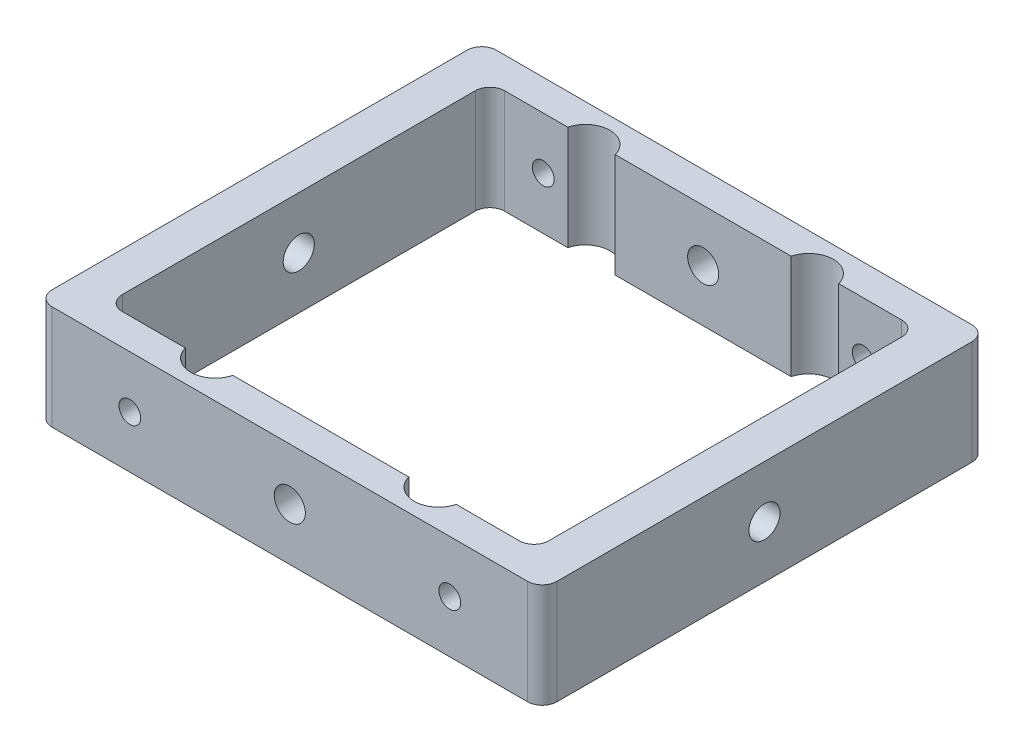
SolidWorks part; units mm, degrees
ref_plane "Front Plane" through (0, 0, 0) normal (0, 0, 1) x (1, 0, 0)
ref_plane "Top Plane" through (0, 0, 0) normal (0, 1, 0) x (1, 0, 0)
ref_plane "Right Plane" through (0, 0, 0) normal (1, 0, 0) x (0, 0, -1)
sketch "Sketch1" plane through (0, 0, 0) normal (0, 1, 0) x (1, 0, 0)
  line L1 (0, 0) -> (60, 0)
  line L2 (0, 0) -> (0, -6.32)
  line L3 (0, -6.32) -> (60, -6.32)
  line L4 (60, 0) -> (60, -6.32)
  dimension "D1" = 60
  dimension "D2" = 6.32
extrude "Boss-Extrude1" add sketch "Sketch1" along normal mid plane 21.28
sketch "Sketch2" plane through (0, 10.64, 0) normal (0, 1, 0) x (1, 0, 0)
  line L0 (0, 0) -> (0, -6.32) construction
  line L1 (0, -6.32) -> (60, -6.32) construction
  line L2 (60, -6.32) -> (60, 0) construction
  circle A0 centre (7.21, 1.25) radius 5
  circle A1 centre (52.79, 1.25) radius 5
  dimension "D1" = 7.21
  dimension "D3" = 7.21
  dimension "D2" = 7.57
  dimension "D4" = 7.57
extrude "Cut-Extrude1" cut sketch "Sketch2" against normal through all
sketch "Sketch3" plane through (60, 0, 0) normal (1, 0, 0) x (0, 0, -1)
  line L1 (-6.32, 10.64) -> (0, 10.64)
  line L2 (-6.32, 10.64) -> (-6.32, -10.64)
  line L3 (-6.32, -10.64) -> (0, -10.64)
  line L4 (0, 10.64) -> (0, -10.64)
extrude "Boss-Extrude2" add sketch "Sketch3" along normal blind 21.5
sketch "Sketch4" plane through (0, 0, 0) normal (-1, 0, 0) x (0, 0, 1)
  line L1 (0, 10.64) -> (6.32, 10.64)
  line L2 (0, 10.64) -> (0, -10.64)
  line L3 (0, -10.64) -> (6.32, -10.64)
  line L4 (6.32, 10.64) -> (6.32, -10.64)
extrude "Boss-Extrude3" add sketch "Sketch4" along normal blind 21.5
sketch "Sketch5" plane through (0, 0, 0) normal (0, 0, -1) x (-1, 0, 0)
  line L5 (-2.3688, -10.64) -> (21.5, -10.64) construction
  line L6 (21.5, 10.64) -> (13.5, 10.64)
  line L7 (21.5, 10.64) -> (21.5, -10.64)
  line L8 (21.5, -10.64) -> (13.5, -10.64)
  line L9 (13.5, 10.64) -> (13.5, -10.64)
  dimension "D1" = 8
extrude "Boss-Extrude6" add sketch "Sketch5" along normal blind 84.33
sketch "Sketch6" plane through (0, 0, 0) normal (0, 0, -1) x (-1, 0, 0)
  line L1 (-81.5, 10.64) -> (-73.5, 10.64)
  line L2 (-81.5, 10.64) -> (-81.5, -10.652)
  line L3 (-81.5, -10.652) -> (-73.5, -10.652)
  line L4 (-73.5, 10.64) -> (-73.5, -10.652)
  dimension "D1" = 8
extrude "Boss-Extrude7" add sketch "Sketch6" along normal blind 84.33
sketch "Sketch7" plane through (73.5, 0, 0) normal (-1, 0, 0) x (0, 0, 1)
  line L0 (-84.33, -10.652) -> (0, -10.652) construction
  line L1 (-84.33, 10.64) -> (-78.01, 10.64)
  line L2 (-84.33, 10.64) -> (-84.33, -10.652)
  line L3 (-84.33, -10.652) -> (-78.01, -10.652)
  line L4 (-78.01, 10.64) -> (-78.01, -10.652)
  dimension "D1" = 6.32
extrude "Boss-Extrude8" add sketch "Sketch7" along normal through all
sketch "Sketch9" plane through (0, 10.64, 0) normal (0, 1, 0) x (1, 0, 0)
  line L0 (-21.5, 84.33) -> (81.5, 84.33) construction
  circle A0 centre (7.21, 76.76) radius 5
  circle A1 centre (52.79, 76.76) radius 5
  dimension "D1" = 7.57
  dimension "D2" = 7.57
  dimension "D3" = 10
extrude "Cut-Extrude2" cut sketch "Sketch9" against normal through all
sketch "Sketch10" plane through (0, 0, -84.33) normal (0, 0, -1) x (-1, 0, 0)
  line L1 (-81.5, -10.64) -> (21.5, -10.64) construction
  line L2 (-30, -10.64) -> (-30, 10.64) construction
  line L3 (21.5, 10.64) -> (-81.5, 10.64) construction
  circle A0 centre (-62.6312, 0.005) radius 2.22
  circle A1 centre (2.6312, 0.005) radius 2.22
  dimension "D1" = 5
  dimension "D2" = 10.645
extrude "Cut-Extrude3" cut sketch "Sketch10" against normal through all
fillet "Fillet1" radius 3 8 edges at (-21.5, 0, 6.32) (81.5, 0, 6.32) (81.5, -0.006, -84.33) (-21.5, -0.006, -84.33) (-13.5, 0, -78.01) (-13.5, 0, 0) (73.5, -0.006, -78.01) (73.5, 0, 0)
sketch "Sketch13" plane through (0, 0, -84.33) normal (0, 0, -1) x (-1, 0, 0)
  line L1 (-78.5, 10.64) -> (-78.5, -10.652) construction
  line L2 (-78.5, -10.64) -> (18.5, -10.64) construction
  circle A0 centre (-30, 0.005) radius 3.175
  dimension "D1" = 48.5
  dimension "D3" = 6.35
  dimension "D2" = 10.645
extrude "Cut-Extrude4" cut sketch "Sketch13" against normal through all
sketch "Sketch16" plane through (0, -10.652, 0) normal (0, -1, 0) x (1, 0, 0)
  line L6 (78.5, -84.33) -> (-18.5, -84.33) construction
  line L7 (25.5729, -84.33) -> (12.6189, -84.33)
  line L8 (25.5729, -84.33) -> (25.5729, -78.01)
  line L9 (25.5729, -78.01) -> (12.6189, -78.01)
  line L10 (12.6189, -84.33) -> (12.6189, -78.01)
  line L11 (12.0512, -78.01) -> (47.9488, -78.01) construction
  dimension "D1" = 12.954
extrude "Cut-Extrude6" [suppressed] cut sketch "Sketch16" against normal mid plane 25.4
sketch "Sketch18" plane through (-21.5, 0, 0) normal (-1, 0, 0) x (0, 0, 1)
  line L0 (-81.33, 10.64) -> (-81.33, -10.652) construction
  line L1 (-75.01, -10.652) -> (0, -10.652) construction
  circle A0 centre (-39.005, -0.007) radius 3.175
  dimension "D1" = 42.325
  dimension "D2" = 10.645
extrude "Cut-Extrude7" cut sketch "Sketch18" against normal through all
